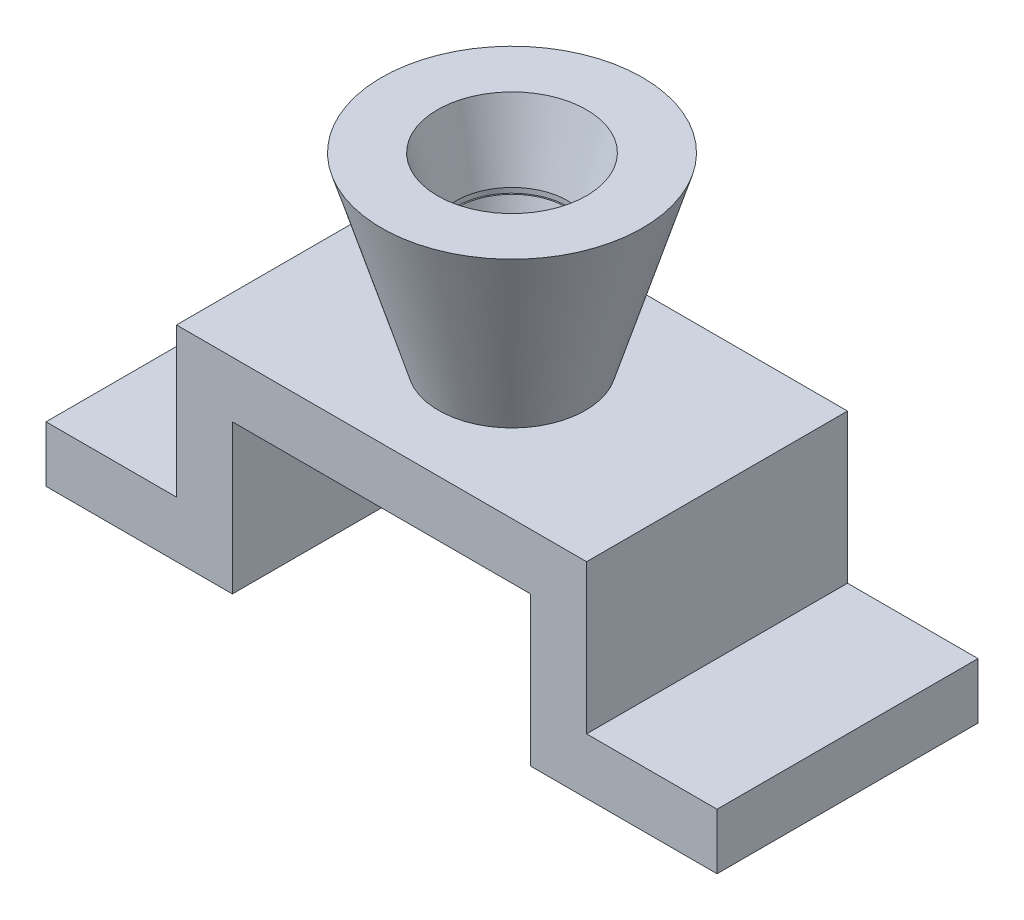
SolidWorks part; units mm, degrees
ref_plane "Front Plane" through (0, 0, 0) normal (0, 0, 1) x (1, 0, 0)
ref_plane "Top Plane" through (0, 0, 0) normal (0, 1, 0) x (1, 0, 0)
ref_plane "Right Plane" through (0, 0, 0) normal (1, 0, 0) x (0, 0, -1)
sketch "Sketch1" plane through (0, 0, 0) normal (0, 0, 1) x (1, 0, 0)
  line L0 (-90, 0) -> (-90, 15)
  line L1 (-90, 15) -> (-55, 15)
  line L2 (-55, 15) -> (-55, 55)
  line L3 (-55, 55) -> (55, 55)
  line L4 (55, 55) -> (55, 15)
  line L5 (55, 15) -> (90, 15)
  line L6 (90, 15) -> (90, 0)
  line L7 (90, 0) -> (40, 0)
  line L8 (40, 0) -> (40, 40)
  line L9 (40, 40) -> (-40, 40)
  line L10 (-40, 40) -> (-40, 0)
  line L11 (-40, 0) -> (-90, 0)
  line L12 (0, 0) -> (0, 85.7286) construction
  point P15 (-215.1395, 21.7442)
  dimension "D1" = 55
  dimension "D2" = 15
  dimension "D3" = 15
  dimension "D4" = 15
  dimension "D5" = 15
  dimension "D6" = 110
  dimension "D7" = 180
extrude "Boss-Extrude1" add sketch "Sketch1" along normal blind 35 and the other way blind 35
sketch "Sketch3" plane through (0, 0, 0) normal (0, 0, 1) x (1, 0, 0)
  line L1 (55, 55) -> (-55, 55) construction
  line L2 (0, 105) -> (35, 105)
  line L3 (35, 105) -> (19.7135, 55)
  line L4 (19.7135, 55) -> (0, 55)
  line L5 (0, 0) -> (0, 119.5475) construction
  line L6 (0, 105) -> (0, 55)
  line L7 (40, 0) -> (90, 0) construction
  dimension "D1" = 73
  dimension "D2" = 105
  dimension "D3" = 35
revolve "Revolve1" add sketch "Sketch3" angle 360 about L5
hole_wizard "Hole1" positions "Sketch4" profile "Sketch5" legacy
sketch "Sketch4" plane through (0, 105, 0) normal (0, 1, 0) x (1, 0, 0)
  point P0 (0, 0)
sketch "Sketch5" plane through (0, 105, 0) normal (1, 0, 0) x (0, 0, 1)
  line L0 (0, 0) -> (0, 20)
  line L1 (0, 20) -> (15, 20)
  line L2 (15, 20) -> (15, 0)
  line L3 (15, 0) -> (0, 0)
  line L4 (0, 110) -> (0, -10) construction
  dimension "Diameter" = 30
  dimension "Depth" = 20
hole_wizard "Hole2" positions "Sketch6" profile "Sketch7" legacy end condition up to next
sketch "Sketch6" plane through (0, 105, 0) normal (0, 1, 0) x (1, 0, 0)
  point P0 (0, 0)
sketch "Sketch7" plane through (0, 105, 0) normal (1, 0, 0) x (0, 0, 1)
  line L0 (0, 0) -> (0, 69.8069)
  line L1 (0, 69.8069) -> (8, 65)
  line L2 (8, 65) -> (8, 44.7846)
  line L3 (8, 44.7846) -> (20, 0)
  line L4 (20, 0) -> (0, 0)
  line L5 (0, -14.3089) -> (0, 102.4216) construction
  line L6 (0, 69.8069) -> (-8, 65) construction
  line L7 (-8, 44.7846) -> (-20, 0) construction
  dimension "Diameter" = 16
  dimension "Depth" = 65
  dimension "C-Sink Diameter" = 40
  dimension "C-Sink Angle" = 30
  dimension "Drill Angle" = 118
